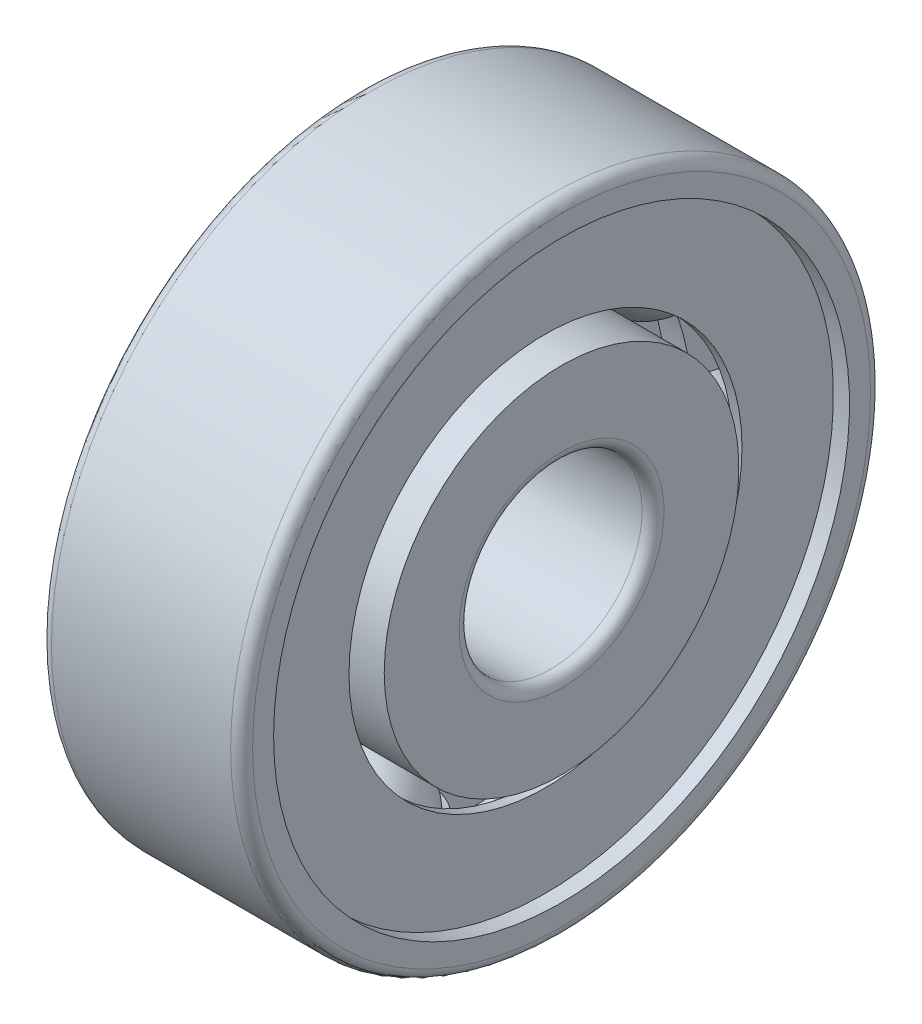
SolidWorks part; units mm, degrees
revolve "凸台-旋转2" add sketch "草图6" angle 360 about L4
sketch "草图6" plane through (0, 0, 0) normal (0, 0, 1) x (1, 0, 0)
  line L0 (0, 0) -> (5.5439, 0) construction
  line L1 (-12.4206, 0) -> (9.8128, 0) construction
  line L2 (0, 0) -> (0, 11.4011) construction
  line L3 (-5.5681, 12.725) -> (6.1049, 12.725) construction
  line L4 (-5.5681, 12.725) -> (6.1049, 12.725) construction
  line L5 (-3.175, 12.725) -> (3.175, 12.725)
  arc A0 (-3.175, 12.725) -> (3.175, 12.725) centre (0, 12.725) ccw
  dimension "Dw" = 6.35
revolve "基体-旋转" add sketch "草图2" angle 360 about L0
sketch "草图2" plane through (0, 0, 0) normal (0, 0, 1) x (1, 0, 0)
  line L0 (-12.4206, 0) -> (9.8128, 0) construction
  line L1 (0, 0) -> (0, 37.3563) construction
  line L2 (-5.5681, 12.725) -> (6.1049, 12.725) construction
  line L3 (-0.6985, 13.5981) -> (0.6985, 13.5981)
  line L4 (-0.6985, 13.5981) -> (-0.6985, 11.8519)
  line L5 (-0.6985, 11.8519) -> (0.6985, 11.8519)
  line L6 (0.6985, 13.5981) -> (0.6985, 11.8519)
  dimension "D1" = 1.397
  dimension "D2" = 0.6985
  dimension "D3" = 1.7462
  dimension "D4" = 0.8731
  dimension "D5" = 12.725
revolve "凸台-旋转1" add sketch "草图3" angle 360 about L1
sketch "草图3" plane through (0, 0, 0) normal (0, 0, 1) x (1, 0, 0)
  line L0 (-5.5681, 12.725) -> (6.1049, 12.725) construction
  line L1 (-5.5681, 12.725) -> (6.1049, 12.725) construction
  line L2 (-12.4206, 0) -> (9.8128, 0) construction
  line L3 (-12.4206, 0) -> (9.8128, 0) construction
  line L4 (0, 0) -> (0, 37.3563) construction
  line L5 (0, 0) -> (0, 37.3563) construction
  line L6 (-3.4925, 12.725) -> (3.4925, 12.725)
  arc A0 (-3.4925, 12.725) -> (3.4925, 12.725) centre (0, 12.725) ccw
  dimension "Dwww" = 6.985
  dimension "D2" = 3.4925
pattern_circular "阵列(圆周)1" count 7 over 360 about axis through (-12.4206, 0, 0) along (1, 0, 0) of "凸台-旋转1"
revolve "凸台-旋转3" add sketch "草图7" angle 360 about L0
sketch "草图7" plane through (0, 0, 0) normal (0, 0, 1) x (1, 0, 0)
  line L0 (0, 0) -> (6.6488, 0) construction
  line L1 (0, 0) -> (0, 16.8954) construction
  line L2 (-4.9, 17.5) -> (4.9, 17.5)
  line L3 (-5.5, 16.9) -> (-5.5, 15.75)
  line L4 (-5.5, 15.75) -> (-0.9309, 15.75)
  line L5 (5.5, 16.9) -> (5.5, 15.75)
  line L6 (0.9309, 15.75) -> (4.0848, 15.75)
  line L7 (4.62, 15.75) -> (5.5, 15.75)
  line L8 (4.0848, 14.75) -> (4.62, 14.75)
  line L9 (4.0848, 14.75) -> (4.0848, 15.75)
  line L11 (4.62, 14.75) -> (4.62, 15.75)
  arc A0 (-4.9, 17.5) -> (-5.5, 16.9) centre (-4.9, 16.9) ccw
  arc A1 (4.9, 17.5) -> (5.5, 16.9) centre (4.9, 16.9) cw
  arc A2 (3.0526, 13.5981) -> (-3.0526, 13.5981) centre (0, 12.725) ccw construction
  arc A3 (0.9644, 15.75) -> (-0.0002, 9.55) centre (0, 12.725) ccw construction
  arc A4 (0.9309, 15.75) -> (-0.9309, 15.75) centre (0, 12.725) ccw
  point P10 (-5.5, 17.5)
  point P13 (5.5, 17.5)
  dimension "D3" = 5.5
  dimension "D4" = 0.5352
  dimension "D5" = 29.5
  dimension "D6" = 0.88
  dimension "B" = 11
ref_plane "基准面1" through (0, 0, 0) normal (0, 0, 1) x (1, 0, 0)
ref_plane "基准面2" through (0, 0, 0) normal (0, 1, 0) x (1, 0, 0)
ref_plane "基准面3" through (0, 0, 0) normal (1, 0, 0) x (0, 0, -1)
sketch "尺寸草图" plane through (0, 0, 0) normal (0, 0, 1) x (1, 0, 0)
  point P0 (0, -75.4307)
  point P1 (6.35, -75.4307)
  point P2 (0, 50.7088)
  point P3 (10, 50.7088)
  point P4 (35, 50.7088)
  point P5 (11, 50.7088)
  point P6 (0, -10.9899)
  point P7 (19.4, -10.9899)
  point P8 (29.5, -10.9899)
  point P9 (0.6, -10.9899)
  point P10 (7, -75.4307)
  dimension "B" = 11
sketch "草图4" plane through (0, 0, 0) normal (0, 0, 1) x (1, 0, 0)
  line L0 (0, 0) -> (8.1272, 0) construction
  line L1 (-12.4206, 0) -> (9.8128, 0) construction
  line L3 (-0.6985, 13.5981) -> (0.6985, 13.5981) construction
  line L4 (-3.4925, 17.0906) -> (3.4925, 17.0906)
  line L5 (-3.4925, 17.0906) -> (-3.4925, 13.5981)
  line L6 (-3.4925, 13.5981) -> (3.4925, 13.5981)
  line L7 (3.4925, 17.0906) -> (3.4925, 13.5981)
revolve "切除-旋转1" cut sketch "草图4" angle 360 about L0
sketch "草图5" plane through (0, 0, 0) normal (0, 0, 1) x (1, 0, 0)
  line L0 (0, 0) -> (8.2665, 0) construction
  line L1 (-12.4206, 0) -> (9.8128, 0) construction
  line L2 (-0.6985, 11.8519) -> (0.6985, 11.8519) construction
  line L3 (-3.4925, 11.8519) -> (3.4925, 11.8519)
  line L4 (-3.4925, 11.8519) -> (-3.4925, 8.3594)
  line L5 (-3.4925, 8.3594) -> (3.4925, 8.3594)
  line L6 (3.4925, 11.8519) -> (3.4925, 8.3594)
revolve "切除-旋转2" cut sketch "草图5" angle 360 about L0
pattern_circular "阵列(圆周)2" count 7 over 360 about axis through (-12.4206, 0, 0) along (1, 0, 0) of "凸台-旋转2"
sketch "草图8" plane through (0, 0, 0) normal (0, 0, 1) x (1, 0, 0)
  line L0 (-12.4206, 0) -> (9.8128, 0) construction
  line L1 (-12.4206, 0) -> (9.8128, 0) construction
  line L2 (5.5, 16.9) -> (5.5, 15.75) construction
  line L3 (-5.5, 9.7) -> (-0.9309, 9.7)
  line L4 (-5.5, 9.7) -> (-5.5, 5.6)
  line L5 (-4.9, 5) -> (4.9, 5)
  line L6 (5.5, 9.7) -> (5.5, 5.6)
  line L7 (-5.5, 16.9) -> (-5.5, 15.75) construction
  line L8 (0.9309, 9.7) -> (5.5, 9.7)
  arc A0 (-5.5, 5.6) -> (-4.9, 5) centre (-4.9, 5.6) ccw
  arc A1 (4.9, 5) -> (5.5, 5.6) centre (4.9, 5.6) ccw
  arc A2 (-3.0526, 11.8519) -> (3.0526, 11.8519) centre (0, 12.725) ccw construction
  arc A3 (-3.0526, 11.8519) -> (3.0526, 11.8519) centre (0, 12.725) ccw construction
  arc A4 (-0.9309, 9.7) -> (0.9309, 9.7) centre (0, 12.725) ccw
  dimension "D1" = 0.6
  dimension "DD" = 10
  dimension "D2" = 0.01
revolve "凸台-旋转4" add sketch "草图8" angle 360 about L1
sketch "草图10" plane through (0, 0, 0) normal (0, 0, 1) x (1, 0, 0)
  line L0 (4.0848, 15.75) -> (4.0848, -15.75) construction
  line L1 (4.62, 14.75) -> (4.0848, 14.75)
  line L2 (4.62, 14.75) -> (4.62, 10.7477)
  line L3 (4.62, 10.7477) -> (4.0848, 10.7477)
  line L4 (4.0848, 14.75) -> (4.0848, 10.7477)
  line L5 (0.9309, 9.7) -> (5.5, 9.7) construction
  line L6 (0, 0) -> (-5.3515, 0) construction
  line L7 (-12.4206, 0) -> (9.8128, 0) construction
  dimension "D1" = 1.0477
revolve "凸台-旋转5" add sketch "草图10" angle 360 about L6
sketch "草图11" plane through (0, 0, 0) normal (1, 0, 0) x (0, 0, -1)
  circle A0 centre (0, 0) radius 17.5
  circle A1 centre (0, 0) radius 17.5 construction
extrude "切除-拉伸1" cut sketch "草图11" against normal blind 10
mirror "镜向所有1" about plane through (0, 0, 0) normal (1, 0, 0) of bodies 109
equation "\"D5@草图7\" = \"防尘圈径D3@尺寸草图\""
equation "\"Z@阵列(圆周)1\"=\"球数Z@尺寸草图\" "
equation "\"Dw@草图6\"=\"球径DW@尺寸草图\""
equation "\"DD@草图8\"=\"d@尺寸草图\""
equation "\"D@草图7\"=\"DD@尺寸草图\""
equation "\"B@草图7\"=\"B@尺寸草图\" "
equation "\"DD2@草图8\"=\"内圈外径DD2@尺寸草图\""
equation "\"R@草图7\"=\"r@尺寸草图\""
equation "\"D3@草图2\" = 0.25*\"Dwww@草图3\""
equation "\"D4@草图2\" = \"D3@草图2\"/2"
equation "\"Dwww@草图3\" = 1.1*\"Dw@草图6\""
equation "\"D2@草图3\" = 0.5*\"Dwww@草图3\""
equation "\"D1@草图2\" = 0.2*\"Dwww@草图3\""
equation "\"D2@草图2\" = 0.5*\"D1@草图2\""
equation "\"切除位置@草图4\" = \"Dwww@草图3\"/2"
equation "\"D1@阵列(圆周)2\" = \"Z@阵列(圆周)1\""
equation "\"D3@草图7\" = \"B@草图7\" / 2"
equation "\"D1@草图8\" = \"R@草图7\""
equation "\"D2@草图7\" = 0.9*\"D@草图7\""
equation "\"D5@草图2\" = 0.25* ( \"D2@草图7\" + \"DD2@草图8\" )  "
equation "\"D6@草图7\" = 0.08 * \"B@草图7\""
equation "\"D1@草图10\" = 0.15*\"Dwww@草图3\""
